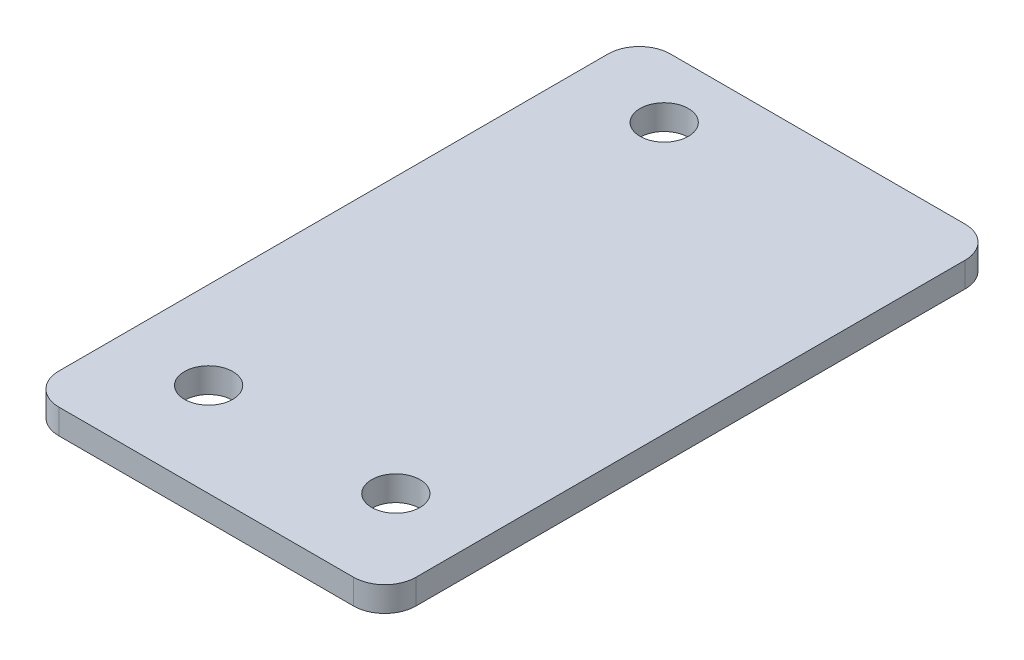
SolidWorks part; units mm, degrees
material "AISI 4340 Steel, normalized"
ref_plane "X-Y Datum" through (0, 0, 0) normal (0, 0, 1) x (1, 0, 0)
ref_plane "X-Z Datum" through (0, 0, 0) normal (0, 1, 0) x (1, 0, 0)
ref_plane "Y-Z Datum" through (0, 0, 0) normal (1, 0, 0) x (0, 0, -1)
sketch "Sketch1" plane through (0, 0, 0) normal (0, 1, 0) x (1, 0, 0)
  line L0 (0, 57.3773) -> (25.4, 57.3773) construction
  line L1 (3.175, -4.8527) -> (33.1644, -4.8527)
  line L2 (0, -1.6777) -> (0, 54.2023)
  line L3 (3.175, 57.3773) -> (33.1644, 57.3773)
  line L4 (36.3394, -1.6777) -> (36.3394, 54.2023)
  arc A0 (36.3394, -1.6777) -> (33.1644, -4.8527) centre (33.1644, -1.6777) cw
  arc A1 (36.3394, 54.2023) -> (33.1644, 57.3773) centre (33.1644, 54.2023) ccw
  arc A2 (0, 54.2023) -> (3.175, 57.3773) centre (3.175, 54.2023) cw
  arc A3 (0, -1.6777) -> (3.175, -4.8527) centre (3.175, -1.6777) ccw
  circle A4 centre (8.89, 51.0273) radius 2.4575 construction
  circle A5 centre (27.94, 4.6723) radius 2.4574 construction
  circle A6 centre (8.89, 4.6723) radius 2.4574 construction
  circle A7 centre (8.89, 51.0273) radius 2.4574
  circle A8 centre (27.94, 4.6723) radius 2.4574
  circle A9 centre (8.89, 4.6723) radius 2.4574
  point P10 (36.3394, -4.8527)
  point P13 (36.3394, 57.3773)
  point P16 (0, 57.3773)
  dimension "D3" = 3.175
  dimension "D1" = 62.23
  dimension "D2" = 36.3394
extrude "Boss-Extrude1" add sketch "Sketch1" against normal blind 2.54
